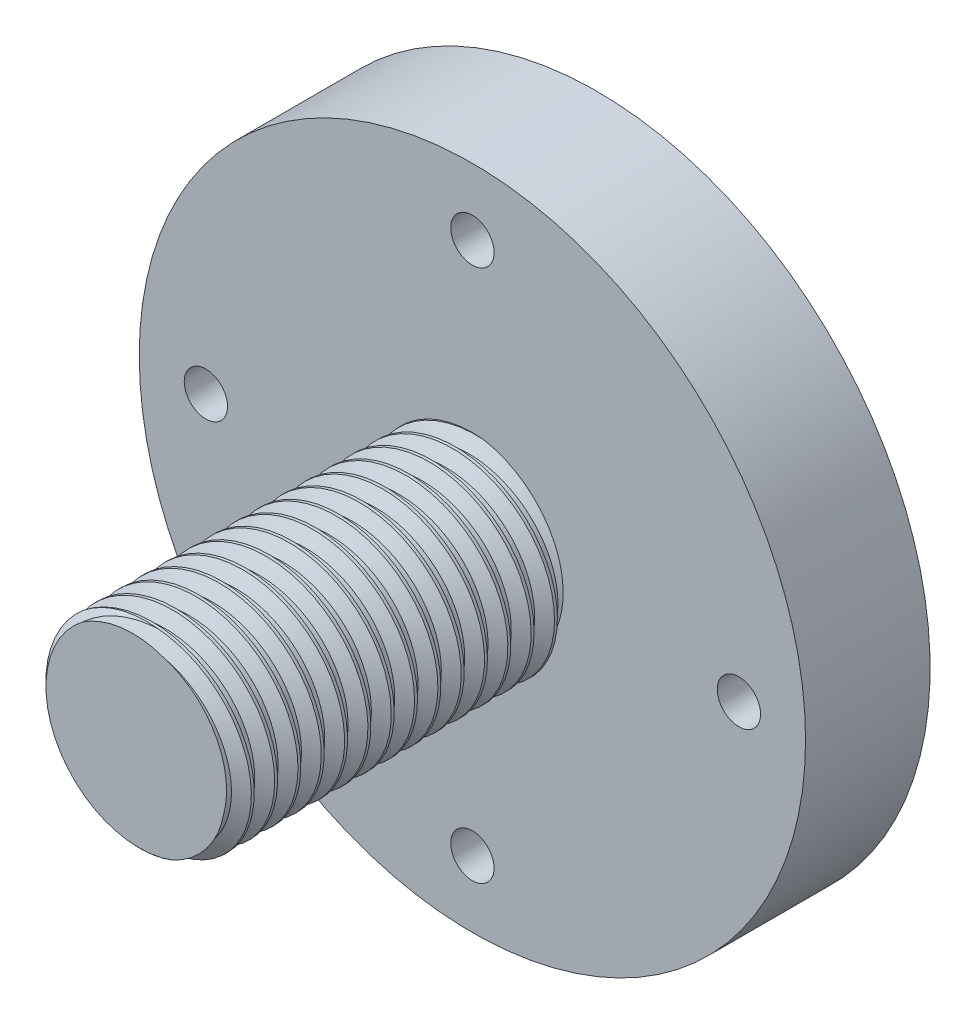
SolidWorks part; units mm, degrees
ref_plane "Front Plane" through (0, 0, 0) normal (0, 0, 1) x (1, 0, 0)
ref_plane "Top Plane" through (0, 0, 0) normal (0, 1, 0) x (1, 0, 0)
ref_plane "Right Plane" through (0, 0, 0) normal (1, 0, 0) x (0, 0, -1)
sketch "Sketch1" plane through (0, 0, 481.4855) normal (0, 0, 1) x (1, 0, 0)
  line L1 (13.2791, -23) -> (26.5581, 0)
  line L2 (26.5581, 0) -> (13.2791, 23)
  line L3 (13.2791, 23) -> (-13.2791, 23)
  line L4 (-13.2791, 23) -> (-26.5581, 0)
  line L5 (-26.5581, 0) -> (-13.2791, -23)
  line L6 (-13.2791, -23) -> (13.2791, -23)
  circle A0 centre (0, 0) radius 23 construction
  dimension "D1" = 46
extrude "Boss-Extrude1" add sketch "Sketch1" along normal blind 18.7
sketch "Sketch2" plane through (0, 0, 500.1855) normal (0, 0, 1) x (1, 0, 0)
  line L0 (-13.2791, 23) -> (-26.5581, 0) construction
  circle A0 centre (0, 0) radius 23
extrude "Cut-Extrude1" cut sketch "Sketch2" against normal through all draft 45 flip side to cut
ref_plane "Plane3" through (0, 0, 490.8355) normal (0, 0, 1) x (1, 0, 0)
mirror "Mirror3" about plane through (0, 0, 490.8355) normal (0, 0, 1) of "Cut-Extrude1"
sketch "Sketch3" plane through (0, 0, 500.1855) normal (0, 0, 1) x (1, 0, 0)
  circle A0 centre (0, 0) radius 15
  dimension "D1" = 30
extrude "Boss-Extrude2" add sketch "Sketch3" along normal blind 50
chamfer "Chamfer1" distance 1 angle 45 1 edges at (15, 0, 550.1855)
thread "Thread1" pitch 3.5 start angle 0, offset 11, length 120, pitch 3.5, diameter 30
ref_plane "Plane6" through (-15, 0, 560.1855) normal (0, -1, 0) x (-1, 0, 0)
sketch "Thread Profile3" plane through (-15, 0, 560.1855) normal (0, -1, 0) x (-1, 0, 0)
  line L0 (0, 0) -> (0, 3.5) construction
  line L11 (0, 0) -> (0, 3.0625)
  line L12 (0, 3.0625) -> (-1.8944, 1.9687)
  line L13 (-1.8944, 1.9687) -> (-1.8944, 1.0937)
  line L15 (-1.8944, 1.0937) -> (0, 0)
  line L17 (-1.8944, 1.5312) -> (0, 1.5312) construction
  point P2 (0, 0)
  dimension "Pitch" = 3.5
  dimension "Profile_Angle" = 60
  dimension "Profile_Land" = 0.875
  dimension "Profile_Height" = 1.8944
sketch "Sketch14" plane through (0, 0, 481.4855) normal (0, 0, -1) x (-1, 0, 0)
  line L0 (0, 50) -> (0, -50) construction
  line L1 (50, 0) -> (-50, 0) construction
  line L2 (13.2791, 23) -> (0, 23)
  line L3 (19.9186, 11.5) -> (13.2791, 23)
  line L4 (13.2791, 23) -> (0, 23) construction
  line L5 (19.9186, 11.5) -> (13.2791, 23) construction
  line L6 (26.5581, 0) -> (19.9186, 11.5)
  line L7 (19.9186, -11.5) -> (26.5581, 0)
  line L8 (26.5581, 0) -> (19.9186, 11.5) construction
  line L9 (19.9186, -11.5) -> (26.5581, 0) construction
  line L10 (0, -23) -> (13.2791, -23)
  line L11 (13.2791, -23) -> (19.9186, -11.5)
  line L12 (0, -23) -> (13.2791, -23) construction
  line L13 (13.2791, -23) -> (19.9186, -11.5) construction
  line L14 (-13.2791, -23) -> (0, -23)
  line L15 (-19.9186, -11.5) -> (-13.2791, -23)
  line L16 (-13.2791, -23) -> (0, -23) construction
  line L17 (-19.9186, -11.5) -> (-13.2791, -23) construction
  line L18 (-13.2791, 23) -> (-19.9186, 11.5)
  line L19 (0, 23) -> (-13.2791, 23)
  line L20 (-13.2791, 23) -> (-19.9186, 11.5) construction
  line L21 (0, 23) -> (-13.2791, 23) construction
  circle A0 centre (0, 0) radius 50
  circle A1 centre (0, 0) radius 40 construction
  arc A2 (19.9186, 11.5) -> (0, 23) centre (0, 0) ccw
  arc A3 (19.9186, 11.5) -> (0, 23) centre (0, 0) ccw construction
  arc A4 (19.9186, -11.5) -> (19.9186, 11.5) centre (0, 0) ccw
  arc A5 (19.9186, -11.5) -> (19.9186, 11.5) centre (0, 0) ccw construction
  arc A6 (0, -23) -> (19.9186, -11.5) centre (0, 0) ccw
  arc A7 (0, -23) -> (19.9186, -11.5) centre (0, 0) ccw construction
  arc A8 (-19.9186, -11.5) -> (0, -23) centre (0, 0) ccw
  arc A9 (-19.9186, -11.5) -> (0, -23) centre (0, 0) ccw construction
  arc A10 (0, 23) -> (-19.9186, 11.5) centre (0, 0) ccw
  arc A11 (0, 23) -> (-19.9186, 11.5) centre (0, 0) ccw construction
  circle A12 centre (40, 0) radius 3.25
  circle A13 centre (0, 40) radius 3.25
  circle A14 centre (-40, 0) radius 3.25
  circle A15 centre (0, -40) radius 3.25
  dimension "D1" = 100
  dimension "D7" = 80
  dimension "D11" = 6.5
  dimension "D2" = 0
  dimension "D3" = 0
  dimension "D4" = 0
  dimension "D5" = 0
  dimension "D6" = 0
extrude "Boss-Extrude3" add sketch "Sketch14" against normal up to surface (18.7 mm away)
